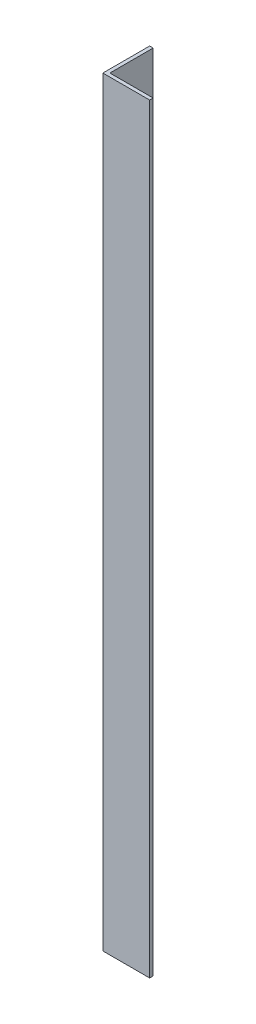
SolidWorks part; units mm, degrees
ref_plane "Спереди" through (0, 0, 0) normal (0, 0, 1) x (1, 0, 0)
ref_plane "Сверху" through (0, 0, 0) normal (0, 1, 0) x (1, 0, 0)
ref_plane "Справа" through (0, 0, 0) normal (1, 0, 0) x (0, 0, -1)
sketch "Эскиз1" plane through (0, 0, 0) normal (0, 1, 0) x (1, 0, 0)
  line L0 (0, 40) -> (0, 0)
  line L1 (0, 0) -> (40, 0)
extrude "Вытянуть-Тонкостенный1" add sketch "Эскиз1" along normal blind 650 thin thin type one direction reverse wall 3
